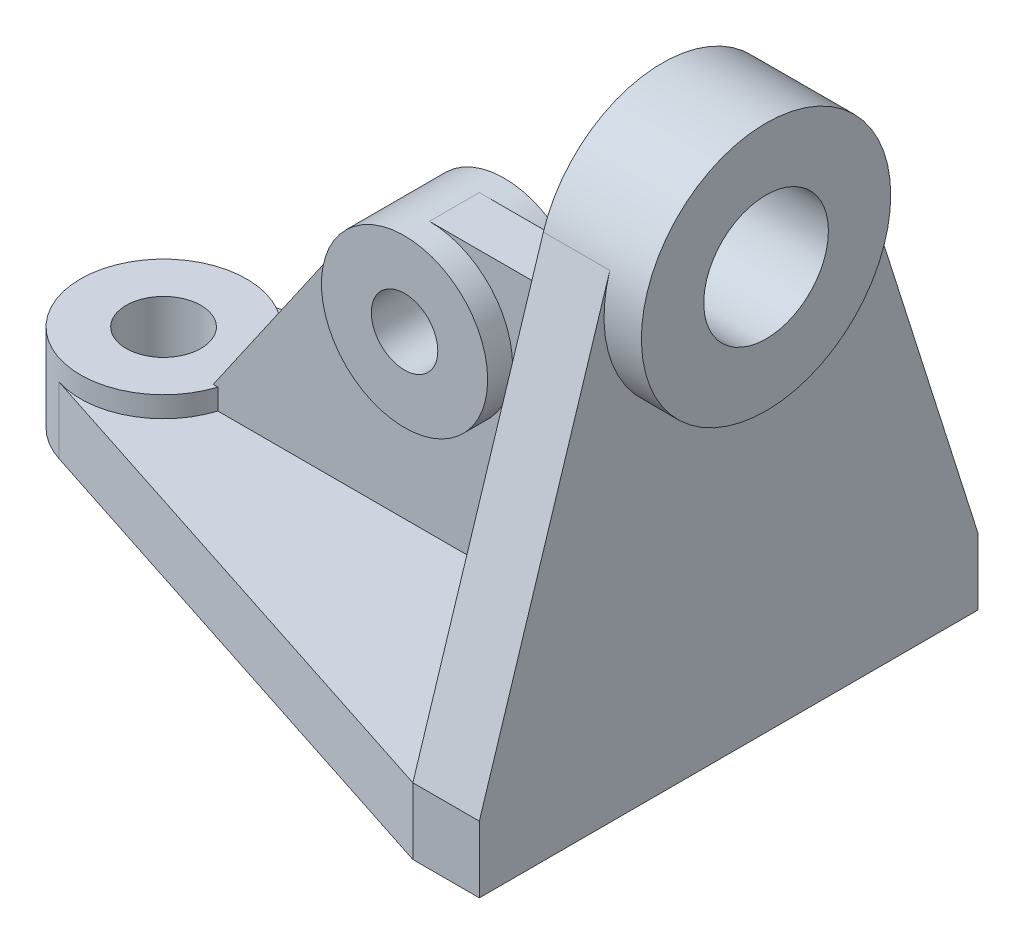
SolidWorks part; units mm, degrees
ref_plane "Front Plane" through (0, 0, 0) normal (0, 0, 1) x (1, 0, 0)
ref_plane "Top Plane" through (0, 0, 0) normal (0, 1, 0) x (1, 0, 0)
ref_plane "Right Plane" through (0, 0, 0) normal (1, 0, 0) x (0, 0, -1)
sketch "Sketch1" plane through (0, 0, 0) normal (0, 1, 0) x (1, 0, 0)
  line L0 (0, 0) -> (120, 0) construction
  line L1 (120, 0) -> (120, 60)
  line L2 (120, 0) -> (120, -60)
  line L3 (120, 60) -> (-6.1777, 19.022)
  line L4 (120, -60) -> (-6.1777, -19.022)
  line L5 (120, -60) -> (136, -60)
  line L6 (136, -60) -> (136, 60)
  line L7 (136, 60) -> (120, 60)
  circle A0 centre (0, 0) radius 20
  circle A1 centre (0, 0) radius 9
  dimension "D1" = 40
  dimension "D2" = 18
  dimension "D3" = 120
  dimension "D4" = 60
  dimension "D5" = 60
  dimension "D6" = 16
extrude "Boss-Extrude3" add sketch "Sketch1" along normal blind 21 contours A1 A0 region at (11.4243, 0, -15.7219)
extrude "Boss-Extrude4" add sketch "Sketch1<5>" along normal blind 16 contours A0 L0 L1 L3 | L0 A0 L4 L2 | L6 L7 L1 L2 L5 region at (73.8068, 0, -22.7388) region at (73.8068, 0, 22.7388) region at (128, 0, 0)
sketch "Sketch1<5>" plane through (0, 0, 0) normal (0, 1, 0) x (1, 0, 0) same geometry as "Sketch1"
sketch "Sketch2" plane through (136, 0, 0) normal (1, 0, 0) x (0, 0, -1)
  line L0 (-60, 16) -> (-28.5976, 115.0651)
  line L1 (60, 16) -> (28.5976, 115.0651)
  circle A0 centre (0, 106) radius 30
  circle A1 centre (0, 106) radius 15
  line M5 (60, 16) -> (-60, 16)
  dimension "D1" = 60
  dimension "D2" = 30
  dimension "D3" = 90
extrude "Boss-Extrude5" add sketch "Sketch2" along normal blind 25 from offset 16 separate body contours A0 A1 region at (136, 77.1912, 4.4567) offset against normal yes
extrude "Boss-Extrude6" add sketch "Sketch2<4>" against normal blind 16 contours A0 L0 L1 M5 region at (136, 48.7404, 0)
sketch "Sketch2<4>" plane through (136, 0, 0) normal (1, 0, 0) x (0, 0, -1) same geometry as "Sketch2"
sketch "Sketch4" plane through (0, 0, 0) normal (0, 0, 1) x (1, 0, 0)
  line L0 (70, 81) -> (120, 81)
  line L1 (120, 16) -> (120, 115.0651) construction
  line L2 (120, 16) -> (-6.1777, 16) construction
  line L3 (17.9549, 21) -> (53.5603, 72.3902)
  line L9 (120, 81) -> (120, 16)
  line L10 (120, 16) -> (20, 16)
  line L11 (20, 21) -> (-20, 21) construction
  line L12 (20, 16) -> (17.9549, 16)
  line L13 (17.9549, 16) -> (17.9549, 21)
  circle A0 centre (70, 61) radius 20
  circle A1 centre (70, 61) radius 8
  dimension "D1" = 16
  dimension "D2" = 40
  dimension "D3" = 50
  dimension "D4" = 45
  dimension "D5" = 70
extrude "Boss-Extrude7" add sketch "Sketch4" along normal mid plane 24 separate body contours A0 A1 region at (83.7421, 74.7421, 0)
extrude "Boss-Extrude9" add sketch "Sketch4<4>" along normal mid plane 12 contours A0 L3 L13 L12 L10 L9 L0 region at (79.9693, 40.7668, 0)
sketch "Sketch4<4>" plane through (0, 0, 0) normal (0, 0, 1) x (1, 0, 0) same geometry as "Sketch4"
